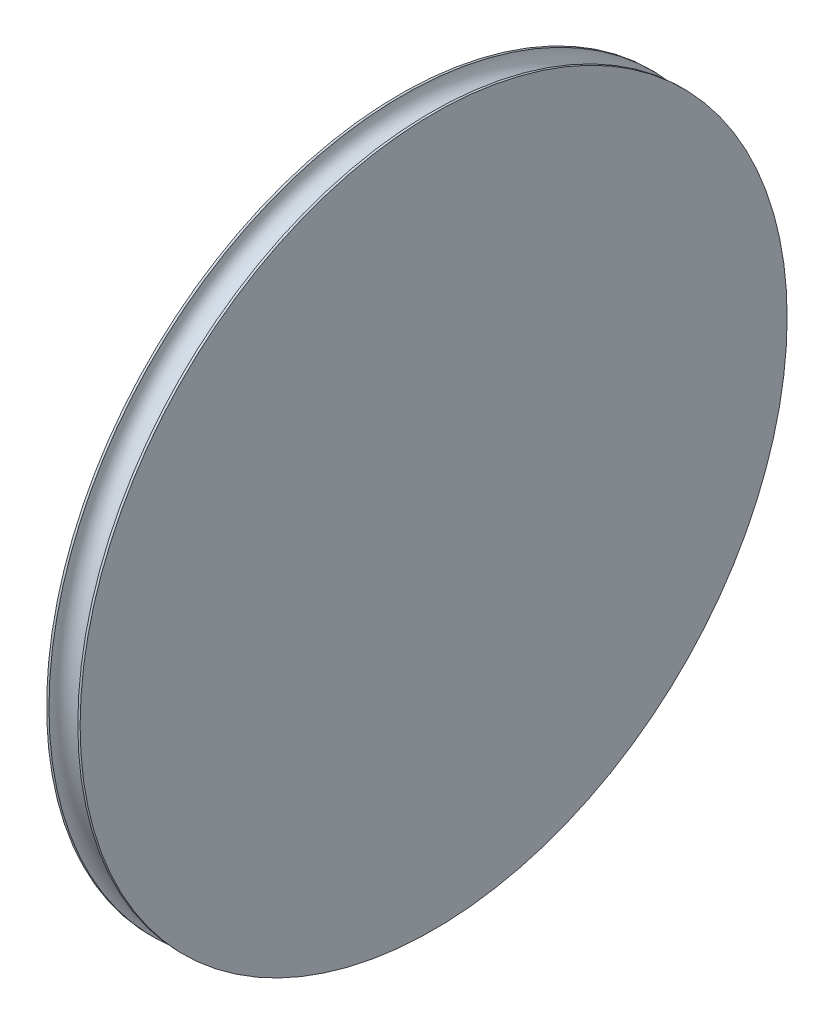
SolidWorks part; units mm, degrees
ref_plane "Front Plane" through (0, 0, 0) normal (0, 0, 1) x (1, 0, 0)
ref_plane "Top Plane" through (0, 0, 0) normal (0, 1, 0) x (1, 0, 0)
ref_plane "Right Plane" through (0, 0, 0) normal (1, 0, 0) x (0, 0, -1)
sketch "Sketch1" plane through (0, 0, 0) normal (1, 0, 0) x (0, 0, -1)
  circle A0 centre (0, 0) radius 38.8938
  dimension "D1" = 77.7875
extrude "Boss-Extrude1" add sketch "Sketch1" along normal blind 3.683
sketch "Sketch10" plane through (0, 0, 0) normal (0, 0, 1) x (1, 0, 0)
  line L0 (3.683, 38.8938) -> (0, 38.8938) construction
  line L1 (-1.0162, 0) -> (5.466, 0) construction
  line L2 (55, 0) -> (-55, 0) construction
  circle A0 centre (1.8415, 38.8938) radius 1.5875
  point P9 (0, 0)
  dimension "D1" = 3.175
revolve "Cut-Revolve1" cut sketch "Sketch10" angle 360 about L1
sketch "Sketch11" plane through (3.683, 0, 0) normal (1, 0, 0) x (0, 0, -1)
  line L2 (0, -50.6508) -> (0, 43.6326) construction
  line L3 (-53.144, 0) -> (47.234, 0) construction
  line L4 (-2.54, 31.6482) -> (-2.54, -31.6482)
  line L5 (2.54, 31.6482) -> (2.54, -31.6482)
  circle A2 centre (0, 0) radius 6.35
  circle A3 centre (0, 0) radius 31.75
  dimension "D1" = 12.7
  dimension "D2" = 63.5
  dimension "D3" = 5.08
  dimension "D4" = 2.54
